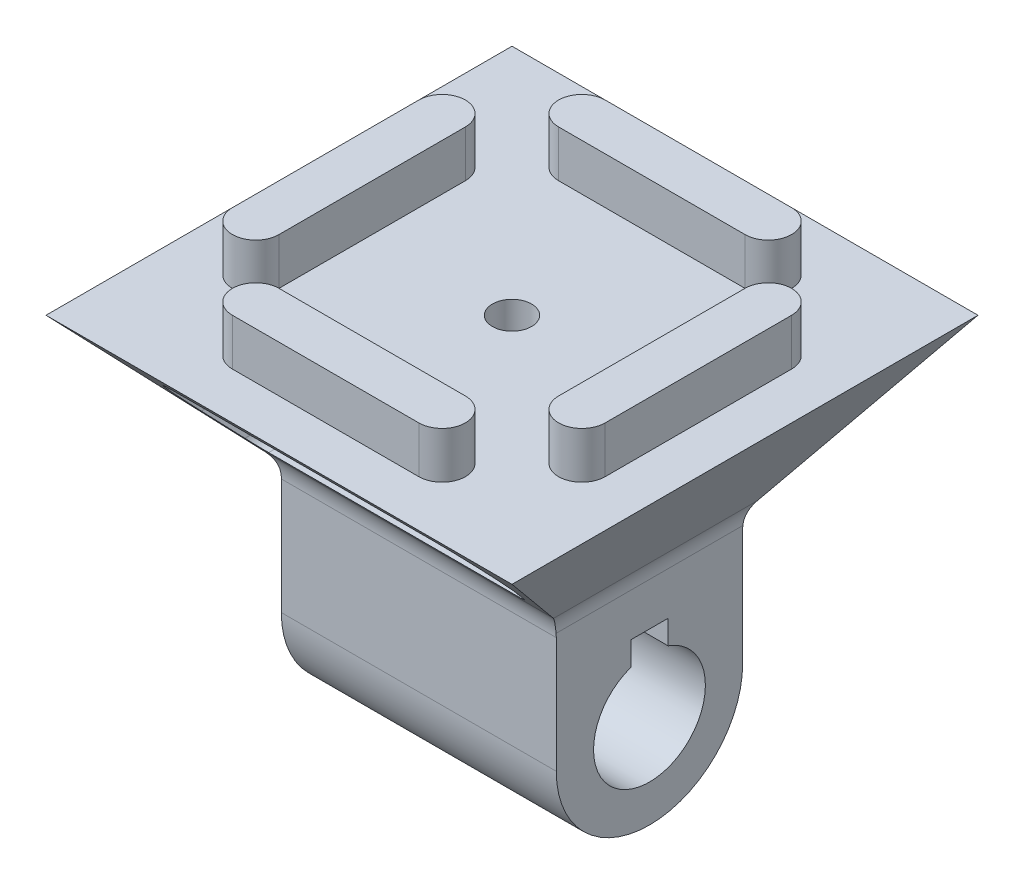
SolidWorks part; units mm, degrees
note: '?' marks a value the reader was unsure of.
material "1060 Alloy"
ref_plane "Front Plane" through (0, 0, 0) normal (0, 0, 1) x (1, 0, 0)
ref_plane "Top Plane" through (0, 0, 0) normal (0, 1, 0) x (1, 0, 0)
ref_plane "Right Plane" through (0, 0, 0) normal (1, 0, 0) x (0, 0, -1)
sketch "Sketch1" plane through (0, 0, 0) normal (1, 0, 0) x (0, 0, -1)
  circle A0 centre (0, 0) radius 6
  circle A1 centre (0, 0) radius 10
  dimension "D1" = 12
  dimension "D2" = 20
extrude "Boss-Extrude1" add sketch "Sketch1" along normal mid plane 29.5
ref_plane "Plane1" through (0, 30, 0) normal (0, 1, 0) x (1, 0, 0)
ref_plane "Plane4" through (0, 14, 0) normal (0, 1, 0) x (1, 0, 0)
sketch "Sketch3" plane through (0, 30, 0) normal (0, 1, 0) x (1, 0, 0)
  line L1 (-25, 25) -> (25, 25)
  line L2 (-25, 25) -> (-25, -25)
  line L3 (-25, -25) -> (25, -25)
  line L4 (25, 25) -> (25, -25)
  line L5 (-25, 25) -> (25, -25) construction
  line L6 (-25, -25) -> (25, 25) construction
  point P0 (0, 0)
  dimension "D1" = 50
sketch "Sketch5" plane through (0, 14, 0) normal (0, 1, 0) x (1, 0, 0)
  line L1 (-14.75, 10) -> (14.75, 10)
  line L3 (-14.75, -10) -> (14.75, -10)
  line L12 (14.75, 10) -> (14.75, -10)
  line L13 (-14.75, -10) -> (-14.75, 10)
  dimension "D1" = 20
  dimension "D2" = 29.5
loft "Loft1" add profiles "Sketch5", "Sketch3" connector at (14.75, 14, -10) connector at (25, 30, -25)
ref_plane "Plane3" through (0, 0, 25) normal (0, 0, 1) x (1, 0, 0)
ref_axis "Axis1" through (0, -43.5149, 0) along (0, 1, 0)?
sketch "Sketch8" plane through (0, 0, 25) normal (0, 0, 1) x (1, 0, 0)
  line L1 (55, 14) -> (-55, 14) construction
  line L2 (68.4482, 30) -> (-68.4482, 30) construction
  line L3 (0, -44.7868) -> (0, 44.7868) construction
  line L4 (-14.75, 14) -> (-25, 30) construction
  line L9 (13.5307, 27) -> (-13.5307, 27)
  line L10 (-16.8765, 20.8833) -> (-14.9789, 17.9211)
  line L11 (-13.2948, 17) -> (13.2948, 17)
  line L12 (14.9789, 17.9211) -> (16.8765, 20.8833)
  arc A0 (13.2948, 17) -> (14.9789, 17.9211) centre (13.2948, 19) ccw
  arc A1 (13.5307, 27) -> (16.8765, 20.8833) centre (13.5307, 23.0266) cw
  arc A2 (-13.5307, 27) -> (-16.8765, 20.8833) centre (-13.5307, 23.0266) ccw
  arc A3 (-14.9789, 17.9211) -> (-13.2948, 17) centre (-13.2948, 19) ccw
  point P17 (0, 27)
  point P20 (0, 17)
  dimension "D1" = 2
  dimension "D2" = 3
  dimension "D3" = 3
sketch "Sketch9" plane through (0, 30, 0) normal (0, 1, 0) x (1, 0, 0)
  line L0 (-17.5, 10) -> (-17.5, -10) construction
  line L1 (-44.2539, 0) -> (44.2539, 0) construction
  line L2 (-15, 10) -> (-15, -10)
  line L3 (-20, 10) -> (-20, -10)
  line L4 (0, -44.7868) -> (0, 44.7868) construction
  line L5 (10, 20) -> (-10, 20)
  line L6 (10, 15) -> (-10, 15)
  line L7 (10, 17.5) -> (-10, 17.5) construction
  line L8 (20, -10) -> (20, 10)
  line L9 (15, -10) -> (15, 10)
  line L10 (17.5, -10) -> (17.5, 10) construction
  line L11 (-10, -20) -> (10, -20)
  line L12 (-10, -15) -> (10, -15)
  line L13 (-10, -17.5) -> (10, -17.5) construction
  arc A0 (-15, 10) -> (-20, 10) centre (-17.5, 10) ccw
  arc A1 (-20, -10) -> (-15, -10) centre (-17.5, -10) ccw
  arc A2 (10, 15) -> (10, 20) centre (10, 17.5) ccw
  arc A3 (-10, 20) -> (-10, 15) centre (-10, 17.5) ccw
  arc A4 (15, -10) -> (20, -10) centre (17.5, -10) ccw
  arc A5 (20, 10) -> (15, 10) centre (17.5, 10) ccw
  arc A6 (-10, -15) -> (-10, -20) centre (-10, -17.5) ccw
  arc A7 (10, -20) -> (10, -15) centre (10, -17.5) ccw
  point P4 (-17.5, 0)
  point P16 (0, 17.5)
  point P23 (17.5, 0)
  point P30 (0, -17.5)
  dimension "D3" = 2.5
  dimension "D1" = 0
  dimension "D2" = 20
  dimension "D4" = 17.5
  dimension "D5" = 4
extrude "Boss-Extrude3" add sketch "Sketch9" along normal blind 5
sketch "Sketch10" plane through (14.75, 0, 0) normal (1, 0, 0) x (0, 0, -1)
  line L0 (0, 44.2539) -> (0, -44.2539) construction
  line L1 (-2, 8.2195) -> (2, 8.2195)
  line L2 (-2, 8.2195) -> (-2, 3.8195)
  line L3 (-2, 3.8195) -> (2, 3.8195)
  line L4 (2, 8.2195) -> (2, 3.8195)
  line L5 (-2, 8.2195) -> (2, 3.8195) construction
  line L6 (-2, 3.8195) -> (2, 8.2195) construction
  point P0 (0, 6.0195)
  dimension "D1" = 4
  dimension "D2" = 2.2
extrude "Cut-Extrude4" cut sketch "Sketch10" against normal through all both and the other way through all
hole_wizard "M5 Tapped Hole1" positions "Sketch11" profile "Sketch13" tap size "M5" standard "ISO"
sketch "Sketch11" plane through (0, 30, 0) normal (0, 1, 0) x (1, 0, 0)
  point P0 (0, 0)
sketch "Sketch13" plane through (0, 30, 0) normal (1, 0, 0) x (0, 0, 1)
  line L0 (0, 0) -> (0, 13.6618)
  line L1 (0, 13.6618) -> (2.1, 12.4)
  line L2 (2.1, 12.4) -> (2.1, 0)
  line L5 (2.1, 0) -> (0, 0)
  line L10 (0, 13.6618) -> (-2.1, 12.4) construction
  line L11 (0, -6.35) -> (0, 107.95) construction
  dimension "Tap Drill Dia." = 4.2
  dimension "Tap Drill Depth" = 12.4
  dimension "Drill Angle" = 118
cosmetic thread "Hole Thread1" parameters "D1"=10, "D2"=5
sketch "Sketch14" plane through (0, 14, 0) normal (0, -1, 0) x (1, 0, 0)
  line L1 (-14.75, 10) -> (14.75, 10)
  line L2 (-14.75, 10) -> (-14.75, -10)
  line L3 (-14.75, -10) -> (14.75, -10)
  line L4 (14.75, 10) -> (14.75, -10)
extrude "Boss-Extrude4" add sketch "Sketch14" along normal up to surface (14 mm away) up to face at (14.75, 0, -10)
extrude "Cut-Extrude6" cut sketch "Sketch8" against normal blind 5 from surface contours L11 A0 L12 A1 L9 A2 L10 A3 starting at face at (-2.5625, 18, 13.75)
mirror "Mirror1" about plane through (0, 0, 0) normal (0, 0, 1) of "Cut-Extrude6"
fillet "Fillet1" radius 4 4 edges
